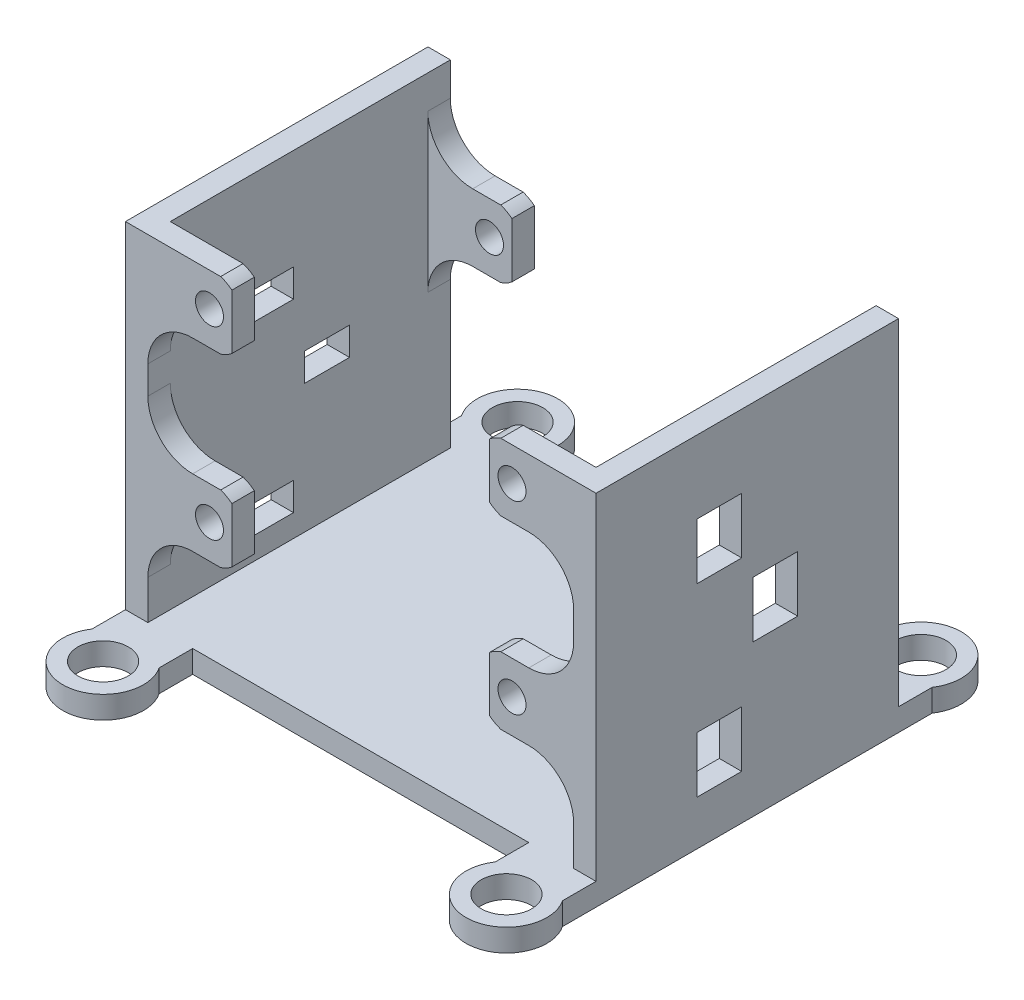
SolidWorks part; units mm, degrees
ref_plane "Спереди" through (0, 0, 0) normal (0, 0, 1) x (1, 0, 0)
ref_plane "Сверху" through (0, 0, 0) normal (0, 1, 0) x (1, 0, 0)
ref_plane "Справа" through (0, 0, 0) normal (1, 0, 0) x (0, 0, -1)
sketch "Эскиз1" plane through (0, 0, 0) normal (0, 1, 0) x (1, 0, 0)
  line L1 (21, -13.5) -> (-21, -13.5)
  line L2 (21, -13.5) -> (21, 13.5)
  line L3 (21, 13.5) -> (-21, 13.5)
  line L4 (-21, -13.5) -> (-21, 13.5)
  line L5 (21, -13.5) -> (-21, 13.5) construction
  line L6 (21, 13.5) -> (-21, -13.5) construction
  point P0 (0, 0)
  dimension "D1" = 42
  dimension "D2" = 27
extrude "Бобышка-Вытянуть1" add sketch "Эскиз1" along normal blind 2
sketch "Эскиз2" plane through (21, 0, 0) normal (1, 0, 0) x (0, 0, -1)
  line L0 (4.5, 2) -> (4.5, 4) construction
  line L1 (-13.5, 2) -> (13.5, 2)
  line L2 (-13.5, 2) -> (-13.5, 32)
  line L3 (-13.5, 32) -> (13.5, 32)
  line L4 (13.5, 2) -> (13.5, 32)
  line L5 (-4.5, 17) -> (-13.5, 17) construction
  line L6 (-4.5, 2) -> (-4.5, 4) construction
  line L7 (-4.5, 4) -> (-13.5, 4) construction
  line L8 (-4.5, 4) -> (-0.5, 4)
  line L9 (-4.5, 4) -> (-4.5, 9)
  line L10 (-4.5, 9) -> (-0.5, 9)
  line L11 (-0.5, 4) -> (-0.5, 9)
  line L12 (0, 32) -> (0, 27.5283) construction
  line L13 (4.5, 4) -> (4.5, 13.5) construction
  line L14 (-4.5, 9) -> (-4.5, 20.5) construction
  line L15 (4.5, 13.5) -> (0.5, 13.5)
  line L16 (4.5, 13.5) -> (4.5, 18.5)
  line L17 (4.5, 18.5) -> (0.5, 18.5)
  line L18 (0.5, 13.5) -> (0.5, 18.5)
  line L20 (-4.5, 20.5) -> (-0.5, 20.5)
  line L21 (-4.5, 20.5) -> (-4.5, 25.5)
  line L22 (-4.5, 25.5) -> (-0.5, 25.5)
  line L23 (-0.5, 20.5) -> (-0.5, 25.5)
  dimension "D1" = 27
  dimension "D2" = 30
  dimension "D3" = 4
  dimension "D4" = 2
  dimension "D5" = 9
  dimension "D6" = 5
  dimension "D7" = 9.5
  dimension "D8" = 4
  dimension "D9" = 5
  dimension "D10" = 11.5
  dimension "D11" = 5
  dimension "D12" = 4
extrude "Бобышка-Вытянуть2" add sketch "Эскиз2" against normal blind 2
mirror "Зеркальное отражение1" about plane through (0, 0, 0) normal (1, 0, 0) of "Бобышка-Вытянуть2"
sketch "Эскиз3" plane through (-21, 0, 0) normal (-1, 0, 0) x (0, 0, 1)
  line L0 (4.5, 25.5) -> (4.5, 20.5) construction
  line L1 (0.5, 25.5) -> (4.5, 25.5)
  line L2 (0.5, 25.5) -> (0.5, 23)
  line L3 (0.5, 23) -> (4.5, 23)
  line L4 (4.5, 25.5) -> (4.5, 23)
  line L5 (-0.5, 18.5) -> (-0.5, 13.5) construction
  line L6 (-4.5, 18.5) -> (-0.5, 18.5)
  line L7 (-4.5, 18.5) -> (-4.5, 16)
  line L8 (-4.5, 16) -> (-0.5, 16)
  line L9 (-0.5, 18.5) -> (-0.5, 16)
  line L10 (4.5, 9) -> (4.5, 4) construction
  line L11 (0.5, 9) -> (4.5, 9)
  line L12 (0.5, 9) -> (0.5, 6.5)
  line L13 (0.5, 6.5) -> (4.5, 6.5)
  line L14 (4.5, 9) -> (4.5, 6.5)
  dimension "D1" = 2.5
  dimension "D2" = 2.5
  dimension "D3" = 2.5
extrude "Бобышка-Вытянуть3" add sketch "Эскиз3" against normal blind 2
sketch "Эскиз4" plane through (0, 0, 13.5) normal (0, 0, -1) x (-1, 0, 0)
  line L0 (-19, 2) -> (-19, 12.5) construction
  line L1 (-19, 2) -> (-19, 32) construction
  line L2 (-19, 12.5) -> (-13.5, 12.5) construction
  line L3 (-19, 9.5) -> (-19, 15.5)
  line L4 (-19, 15.5) -> (-12.5, 15.5)
  line L5 (-19, 9.5) -> (-12.5, 9.5)
  line L6 (-13.5, 12.5) -> (-11.5, 12.5) construction
  line L7 (-11.5, 14.9495) -> (-11.5, 10.0505)
  circle A0 centre (-13.5, 12.5) radius 1.25
  arc A1 (-12.5, 15.5) -> (-11.5, 14.9495) centre (-13.5, 12.5) cw
  arc A2 (-11.5, 10.0505) -> (-12.5, 9.5) centre (-13.5, 12.5) cw
  dimension "D3" = 2.5
  dimension "D1" = 10.5
  dimension "D2" = 5.5
  dimension "D4" = 2
  dimension "D5" = 3
extrude "Бобышка-Вытянуть4" add sketch "Эскиз4" along normal blind 2
mirror "Зеркальное отражение2" about plane through (0, 0, 0) normal (1, 0, 0) of "Бобышка-Вытянуть4"
sketch "Эскиз7" plane through (19, 0, 0) normal (-1, 0, 0) x (0, 0, 1)
  line L0 (13.5, 2) -> (13.5, 12.5) construction
  line L1 (-13.5, 2) -> (-13.5, 22.8) construction
  line L2 (-13.5, 2) -> (-13.5, 32) construction
  line L3 (13.5, 12.5) -> (-13.5, 22.8) construction
  dimension "D1" = 10.5
  dimension "D2" = 20.8
pattern_linear "Линейный массив1" count 2 spacing 16.5 along (0, 1, 0) of "Зеркальное отражение2"
pattern_linear "Линейный массив2" count 2 spacing 26.75 along (0, 0.3564, -0.9343) of "Зеркальное отражение2"
fillet "Скругление1" radius 4 10 edges at (19, 15.5, 12.5) (19, 9.5, 12.5) (-19, 9.5, 12.5) (-19, 15.5, 12.5) (19, 26, 12.5) (-19, 26, 12.5) (-19, 19.0344, -12.4931) (-19, 25.0344, -12.4931) (19, 25.0344, -12.4931) (19, 19.0344, -12.4931)
sketch "Эскиз8" plane through (0, 0, 0) normal (0, 1, 0) x (1, 0, 0)
  line L0 (-21, 13.5) -> (-18, 13.4931)
  line L1 (-15, 13.4931) -> (-19, 13.4931) construction
  line L2 (-18, 13.4931) -> (-18, 18.4931) construction
  line L3 (-21, 13.5) -> (-21, 16.4931)
  line L4 (-15, 13.5) -> (-18, 13.4931)
  line L5 (-15, 13.5) -> (-15, 16.4931)
  circle A0 centre (-18, 18.4931) radius 2.25
  arc A1 (-21, 16.4931) -> (-15, 16.4931) centre (-18, 18.4931) cw
  dimension "D3" = 4.5
  dimension "D1" = 3
  dimension "D2" = 5
extrude "Бобышка-Вытянуть5" add sketch "Эскиз8" along normal blind 2
mirror "Зеркальное отражение3" about plane through (0, 0, 0) normal (1, 0, 0) of "Бобышка-Вытянуть5"
mirror "Зеркальное отражение4" about plane through (0, 0, 0) normal (0, 0, 1) of "Зеркальное отражение3"
